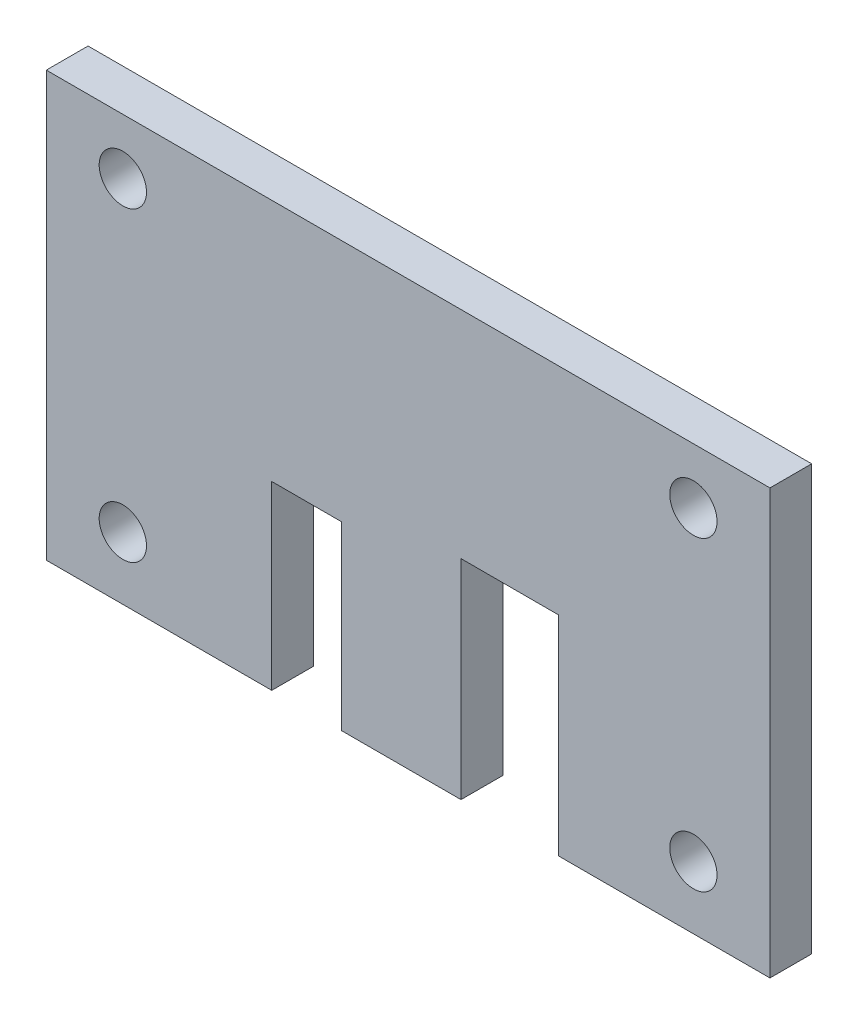
SolidWorks part; units mm, degrees
ref_plane "Front Plane" through (0, 0, 0) normal (0, 0, 1) x (1, 0, 0)
ref_plane "Top Plane" through (0, 0, 0) normal (0, 1, 0) x (1, 0, 0)
ref_plane "Right Plane" through (0, 0, 0) normal (1, 0, 0) x (0, 0, -1)
ref_plane "PY124_4" through (0, 0, 124.4) normal (0, 0, 1) x (1, 0, 0)
sketch "Sketch1" plane through (0, 0, 124.4) normal (0, 0, 1) x (1, 0, 0)
  line L0 (-62.5, -24) -> (-10.5, -24)
  line L1 (-10.5, -24) -> (-10.5, 6.5)
  line L2 (-10.5, 6.5) -> (-62.5, 6.5)
  line L3 (-62.5, 6.5) -> (-62.5, -24)
extrude "Cover Plate" add sketch "Sketch1" along normal blind 3
ref_plane "PY123_4" through (0, 0, 123.4) normal (0, 0, 1) x (1, 0, 0)
sketch "Sketch2" plane through (0, 0, 123.4) normal (0, 0, 1) x (1, 0, 0)
  line L0 (-46.3, -25) -> (-41.3, -25)
  line L1 (-41.3, -25) -> (-41.3, -11)
  line L2 (-41.3, -11) -> (-46.3, -11)
  line L3 (-46.3, -11) -> (-46.3, -25)
  line L4 (-32.7, -25) -> (-25.7, -25)
  line L5 (-25.7, -25) -> (-25.7, -9)
  line L6 (-25.7, -9) -> (-32.7, -9)
  line L7 (-32.7, -9) -> (-32.7, -25)
extrude "Cable Notches" cut sketch "Sketch2" along normal blind 5
sketch "Sketch3" plane through (0, 0, 123.4) normal (0, 0, 1) x (1, 0, 0)
  circle A0 centre (-57, -19.5) radius 1.7
  circle A1 centre (-57, 2.5) radius 1.7
  circle A2 centre (-16, -19.5) radius 1.7
  circle A3 centre (-16, 2.5) radius 1.7
extrude "Screw Holes" cut sketch "Sketch3" along normal blind 5
equation "\"BOARD_REAR\" = 86.0"
equation "\"BOARD_FRONT\" = 41.0"
equation "\"BOARD_END\" = 22.0"
equation "\"BOARD_ANGLED\" = 30.0"
equation "\"BOARD_DEPTH\" = 41.8431"
equation "\"PCB_T\" = 1.6"
equation "\"ABOVE_PCB\" = 14.0"
equation "\"BELOW_PCB\" = 6.0"
equation "\"MID_PARTS_H\" = 9.0"
equation "\"BOARD_HOLE_PILOT\" = 1.6"
equation "\"J2_X\" = 19.0"
equation "\"DUPONT_DROP\" = 14.0"
equation "\"BEND_R\" = 5.0"
equation "\"BOARD_GAP\" = 3.0"
equation "\"TOF_FOV\" = 25.0"
equation "\"TOF_MARGIN_DEG\" = 5.0"
equation "\"TOF_WIN_MARGIN\" = 1.0"
equation "\"TOF_Z\" = 9.0"
equation "\"TOF_SIDE_BEARING\" = 90.0"
equation "\"TOF_CONE_LEN\" = 70.0"
equation "\"CAM_W\" = 29.2"
equation "\"CAM_H\" = 28.2"
equation "\"CAM_D\" = 12.35"
equation "\"CAM_FRONT_Y\" = 43.0"
equation "\"CAM_BOTTOM_Z\" = 17.0"
equation "\"CAM_LENS_UP\" = 11.6"
equation "\"CAM_LENS_OPEN\" = 9.6"
equation "\"CAM_HFOV\" = 53.5"
equation "\"CAM_VFOV\" = 41.41"
equation "\"CAM_FOV_MARGIN\" = 3.0"
equation "\"CAM_FIT\" = 0.3"
equation "\"RIBBON_W\" = 16.0"
equation "\"RIBBON_T\" = 0.3"
equation "\"RIBBON_LEN\" = 150.0"
equation "\"RIBBON_EXIT_Y\" = 35.0"
equation "\"WALL\" = 2.4"
equation "\"HEAD_X\" = 48.4"
equation "\"HEAD_REAR_Y\" = -11.9"
equation "\"CAM_FOAM\" = 2.8"
equation "\"HEAD_FRONT_Y\" = 48.2"
equation "\"HEAD_TOP_Z\" = 50.6"
equation "\"HEAD_BOT_Z\" = -28.4"
equation "\"HEAD_SPLIT_Z\" = -4.0"
equation "\"SKIRT_T\" = 1.2"
equation "\"SKIRT_H\" = 3.0"
equation "\"SKIRT_FIT\" = 0.3"
equation "\"VISOR\" = 7.8"
equation "\"VISOR_Z\" = 40.0"
equation "\"ROOF_SLOPE_Y\" = 40.0"
equation "\"ROOF_CHAMFER\" = 10.0"
equation "\"REAR_CHAMFER\" = 10.0"
equation "\"CORNER_CHAMFER\" = 6.0"
equation "\"LOWER_SIDE_FACET\" = 6.0"
equation "\"LIGHTBAR_DEPTH\" = 1.0"
equation "\"HOOD_Z\" = 14.0"
equation "\"HOOD_L\" = 6.0"
equation "\"SIDE_HOOD_L\" = 4.0"
equation "\"INSERT_M3_D\" = 4.0"
equation "\"INSERT_M3_L\" = 6.0"
equation "\"M3_CLEAR\" = 3.4"
equation "\"M2_PILOT\" = 1.6"
equation "\"M25_PILOT\" = 2.2"
equation "\"BOX_X\" = 72.4"
equation "\"BOX_FRONT_Y\" = -11.9"
equation "\"BOX_REAR_Y\" = -124.4"
equation "\"BOX_BOT_Z\" = -28.4"
equation "\"BOX_TOP_Z\" = 28.0"
equation "\"LID_T\" = 2.4"
equation "\"LID_SKIRT\" = 1.6"
equation "\"LID_TONGUE_H\" = 3.0"
equation "\"LID_FIT\" = 0.3"
equation "\"PI_STANDOFF\" = 10.0"
equation "\"BOX_REAR_CHAMFER\" = 8.0"
equation "\"BOX_REAR_FACET\" = 4.0"
equation "\"VENT_UPSTAND\" = 3.0"
equation "\"TUBE_D\" = 22.2"
equation "\"TUBE_LINER\" = 1.0"
equation "\"MOUNT_Y\" = -70.0"
equation "\"RAIL_W\" = 30.0"
equation "\"RAIL_W2\" = 38.0"
equation "\"RAIL_H\" = 6.0"
equation "\"SLIDE\" = 0.3"
equation "\"STOP_T\" = 6.0"
equation "\"CLAMP_W\" = 40.0"
equation "\"CLAMP_HALF\" = 20.0"
equation "\"CLAMP_DROP\" = 12.0"
equation "\"CAP_T\" = 12.0"
equation "\"CLAMP_BOLT_OFF\" = 16.6"
equation "\"M5_INSERT_D\" = 6.4"
equation "\"M5_CLEAR\" = 5.5"
equation "\"LOCK_D\" = 3.3"
equation "\"POD_TILT_DEG\" = 0.0"
equation "\"PRINT_LIMIT\" = 180.0"
equation "\"PI5_L\" = 85.0"
equation "\"PI5_W\" = 56.0"
equation "\"PI5_T\" = 1.6"
equation "\"PI5_USBC_BX\" = 11.2"
equation "\"PI5_ETH_BY\" = 10.2"
equation "\"PI5_PORT_OVERHANG\" = 3.0"
equation "\"PI5_FPC_H\" = 5.0"
equation "\"PI5_FPC_USE\" = 0.0"
equation "\"PI5_PIN1_BX\" = 8.37"
equation "\"HEADER_BASE_H\" = 2.5"
equation "\"DUPONT_L\" = 14.0"
equation "\"PI5_UNDERSIDE\" = 1.5"
equation "\"COOLER_H\" = 15.0"
equation "\"HAT_W\" = 65.0"
equation "\"HAT_D\" = 56.5"
equation "\"HAT_T\" = 1.6"
equation "\"HAT_SPACER\" = 16.0"
equation "\"HAILO_H\" = 10.0"
equation "\"STACK_PINS_H\" = 6.0"
equation "\"DUPONT_SEAT\" = 0.5"
equation "\"PCIE_FFC_LOOP\" = 6.0"
equation "\"HAILO_AIR_GAP_MIN\" = 8.0"
equation "\"M25_CLEAR\" = 2.7"
equation "\"PI_X0\" = -55.0"
equation "\"PI_Y1\" = -36.5"
equation "\"PI_Y0\" = -92.5"
equation "\"BOX_LEN\" = 112.5"
equation "\"COVER_T\" = 3.0"
equation "\"COVER_TOP_Z\" = 6.5"
equation "\"SIDE_LEDGE_Z\" = -0.5"
equation "\"UPPER_LEDGE_Z\" = 17.0"
equation "\"REAR_LEDGE_Z\" = 8.0"
equation "\"LEDGE_L\" = 4.0"
equation "\"LEDGE_TIP\" = 1.5"
equation "\"RIBBON_W_PI\" = 11.5"
equation "\"RIBBON_RUN_Z\" = 12.0"
equation "\"RIBBON_SPEC_LEN\" = 200.0"
